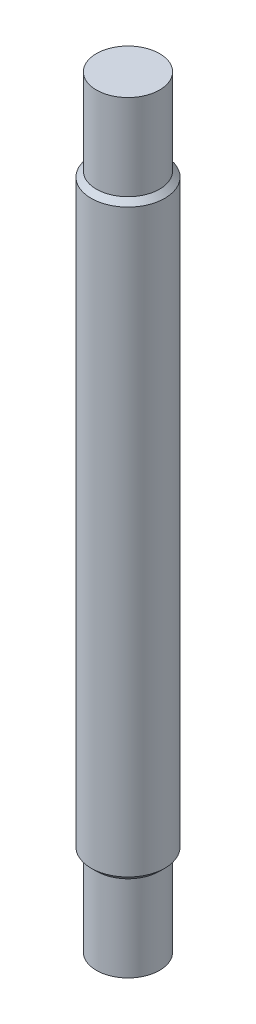
SolidWorks part; units mm, degrees
ref_plane "Front Plane" through (0, 0, 0) normal (0, 0, 1) x (1, 0, 0)
ref_plane "Top Plane" through (0, 0, 0) normal (0, 1, 0) x (1, 0, 0)
ref_plane "Right Plane" through (0, 0, 0) normal (1, 0, 0) x (0, 0, -1)
sketch "Sketch1" plane through (0, 0, 0) normal (0, 1, 0) x (1, 0, 0)
  circle A0 centre (0, 0) radius 22.225
  dimension "D1" = 44.45
extrude "Boss-Extrude1" add sketch "Sketch1" along normal blind 230 and the other way blind 230
ref_plane "Plane1" through (0, 230, 0) normal (0, 1, 0) x (1, 0, 0)
sketch "Sketch2" plane through (0, 230, 0) normal (0, 1, 0) x (1, 0, 0)
  circle A0 centre (0, 0) radius 19.05
  circle A1 centre (0, 0) radius 25.4
  dimension "D1" = 38.1
  dimension "D2" = 50.8
extrude "Cut-Extrude1" cut sketch "Sketch2" against normal blind 50
chamfer "Chamfer1" distance 5 angle 45 1 edges at (0, 180, 22.225)
ref_plane "Plane2" through (0, -230, 0) normal (0, -1, 0) x (-1, 0, 0)
sketch "Sketch3" plane through (0, -230, 0) normal (0, -1, 0) x (-1, 0, 0)
  circle A0 centre (0, 0) radius 19.05
  circle A1 centre (0, 0) radius 25.4
  dimension "D1" = 38.1
  dimension "D2" = 50.8
extrude "Cut-Extrude2" cut sketch "Sketch3" against normal blind 50
chamfer "Chamfer2" distance 5 angle 45 1 edges at (0, -180, -22.225)
